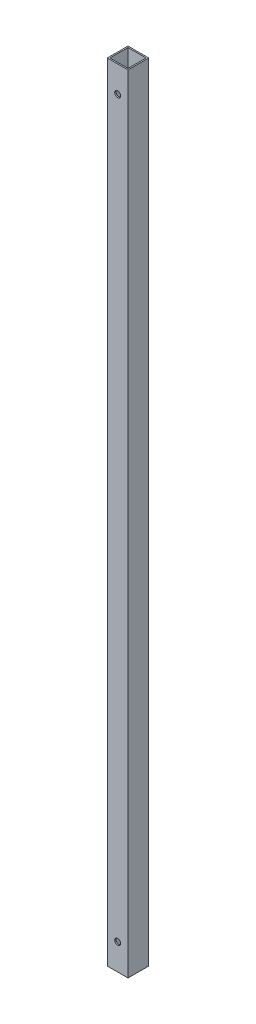
SolidWorks part; units mm, degrees
ref_plane "Front Plane" through (0, 0, 0) normal (0, 0, 1) x (1, 0, 0)
ref_plane "Top Plane" through (0, 0, 0) normal (0, 1, 0) x (1, 0, 0)
ref_plane "Right Plane" through (0, 0, 0) normal (1, 0, 0) x (0, 0, -1)
sketch "Sketch1" plane through (0, 0, 0) normal (0, 1, 0) x (1, 0, 0)
  line L0 (-6.9, -6.9) -> (-6.9, 6.9)
  line L1 (-7.9, -7.9) -> (7.9, -7.9)
  line L2 (-7.9, -7.9) -> (-7.9, 7.9)
  line L3 (-7.9, 7.9) -> (7.9, 7.9)
  line L4 (7.9, -7.9) -> (7.9, 7.9)
  line L5 (-7.9, -7.9) -> (7.9, 7.9) construction
  line L6 (-7.9, 7.9) -> (7.9, -7.9) construction
  line L7 (-6.9, 6.9) -> (6.9, 6.9)
  line L8 (6.9, -6.9) -> (6.9, 6.9)
  line L9 (-6.9, -6.9) -> (6.9, -6.9)
  point P0 (0, 0)
  dimension "D1" = 1
extrude "Boss-Extrude1" add sketch "Sketch1" along normal blind 600
sketch "Sketch3" plane through (0, 0, 7.9) normal (0, 0, 1) x (1, 0, 0)
  circle A0 centre (0, 580) radius 2.25
  circle A1 centre (0, 20) radius 2.25
  dimension "D1" = 4.5
  dimension "D2" = 4.5
extrude "Cut-Extrude2" cut sketch "Sketch3" against normal through all
